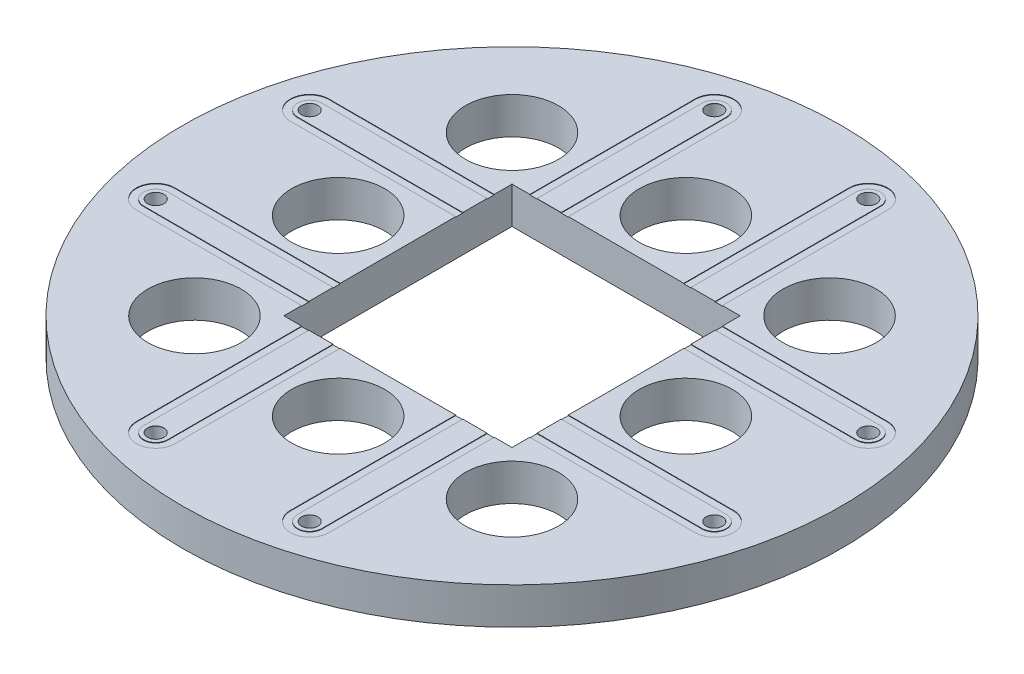
SolidWorks part; units mm, degrees
material "Ceramic Porcelain"
ref_plane "Front Plane" through (0, 0, 0) normal (0, 0, 1) x (1, 0, 0)
ref_plane "Top Plane" through (0, 0, 0) normal (0, 1, 0) x (1, 0, 0)
ref_plane "Right Plane" through (0, 0, 0) normal (1, 0, 0) x (0, 0, -1)
ref_axis "Y Axis" through (0, 0.0762, 0) along (0, -1, 0)
sketch "Boday Sketch" plane through (0, 0, 0) normal (0, 1, 0) x (1, 0, 0)
  circle A0 centre (0, 0) radius 11.557
  dimension "D1" = 23.114
extrude "Body" add sketch "Boday Sketch" against normal blind 1.27
sketch "Copper Sketch" plane through (0, 0, 0) normal (0, 1, 0) x (1, 0, 0)
  circle A0 centre (0, 0) radius 11.557
  dimension "D1" = 23.114
extrude "Copper" add sketch "Copper Sketch" along normal blind 0.0175
sketch "IO Hole Positions" plane through (0, 0, 0) normal (0, 1, 0) x (1, 0, 0)
  line L0 (-11.557, 0) -> (11.557, 0) construction
  circle A1 centre (0, 0) radius 11.557 construction
  point P1 (-2.7, 9.7947)
  point P8 (-2.7, -9.7947)
  dimension "D2" = 2.7
sketch "Gap" plane through (0, 0, 0) normal (0, 1, 0) x (1, 0, 0)
  line L10 (-3.375, 9.7947) -> (-3.375, -9.7947)
  line L11 (-11.557, 0) -> (11.557, 0) construction
  line L12 (-3.375, 0) -> (-2.025, 0) construction
  line L13 (-2.025, -9.7947) -> (-2.025, 9.7947)
  arc A5 (-2.025, 9.7947) -> (-3.375, 9.7947) centre (-2.7, 9.7947) ccw
  arc A6 (-2.025, -9.7947) -> (-3.375, -9.7947) centre (-2.7, -9.7947) cw
  dimension "D1" = 0.675
sketch "Center Sketch" plane through (0, 0, 0) normal (0, 1, 0) x (1, 0, 0)
  line L6 (-3.125, 9.7947) -> (-3.125, -9.7947)
  line L7 (-11.557, 0) -> (11.557, 0) construction
  line L8 (-3.125, 0) -> (-2.275, 0) construction
  line L9 (-2.275, -9.7947) -> (-2.275, 9.7947)
  arc A3 (-2.275, 9.7947) -> (-3.125, 9.7947) centre (-2.7, 9.7947) ccw
  arc A4 (-2.275, -9.7947) -> (-3.125, -9.7947) centre (-2.7, -9.7947) cw
  dimension "D1" = 0.425
extrude "Gap Cut" cut sketch "Gap" along normal through all
extrude "Center" add sketch "Center Sketch" along normal blind 0.0175 separate body
sketch "IO Hole Sketch" plane through (0, 0, 0) normal (0, 1, 0) x (1, 0, 0)
  circle A1 centre (-2.7, 9.7947) radius 0.287
  circle A3 centre (-2.7, -9.7947) radius 0.287
  dimension "D1" = 0.574
  dimension "D2" = 0.574
extrude "IO Hole" cut sketch "IO Hole Sketch" against normal through all and the other way through all
pattern_circular "Gap Cuts" count 4 over 360 about axis through (0, 0.0762, 0) along (0, -1, 0) of "Gap Cut"
pattern_circular "Centers" count 4 over 360 about axis through (0, 0.0762, 0) along (0, -1, 0) of "Center"
pattern_circular "IO Holes" count 4 over 360 about axis through (0, 0.0762, 0) along (0, -1, 0) of "IO Hole"
sketch "Pocket Sketch" plane through (0, 0, 0) normal (0, 1, 0) x (1, 0, 0)
  line L1 (-4, -4) -> (4, -4)
  line L2 (-4, -4) -> (-4, 4)
  line L3 (-4, 4) -> (4, 4)
  line L4 (4, -4) -> (4, 4)
  line L5 (-4, -4) -> (4, 4) construction
  line L6 (-4, 4) -> (4, -4) construction
  point P0 (0, 0)
  dimension "D1" = 8
  dimension "D2" = 8
extrude "Pocket" cut sketch "Pocket Sketch" against normal through all and the other way through all
sketch "Posts" plane through (0, 0, 0) normal (0, 1, 0) x (1, 0, 0)
  circle A0 centre (0, 6.096) radius 1.632
  circle A8 centre (-5.5678, 5.5678) radius 1.6319
  point P0 (0, 6.096)
  point P4 (-5.5678, 5.5678)
  dimension "D2" = 3.2639
  dimension "D4" = 3.2639
  dimension "D1" = 6.096
  dimension "D3" = 7.874
  dimension "D5" = 6.096
extrude "Post Cut" cut sketch "Posts" against normal through all and the other way through all
pattern_circular "Post Cuts" count 4 over 360 about axis through (0, 0.0762, 0) along (0, -1, 0) of "Post Cut"
equation "\"mount_d\"= 0.91in"
equation "\"dieletric_h\"= 0.05in"
equation "\"D1@Boday Sketch\" = \"mount_d\""
equation "\"D1@Body\" = \"dieletric_h\""
equation "\"screw_inner_r\"= 0.415in"
equation "\"io_r\"= 0.4in"
equation "\"io_hole_d\"= 0.574mm"
equation "\"W\"= 0.85mm"
equation "\"G\"= 0.25mm"
equation "\"copper_t\"= 17.5um"
equation "\"silicon_size\"= 8mm"
equation "\"D1@Center\" = \"copper_t\""
equation "\"D1@Copper\"=\"copper_t\""
equation "\"D1@Pocket Sketch\" = \"silicon_size\""
equation "\"D2@Pocket Sketch\" = \"silicon_size\""
equation "\"post_r1\" = 0.24in"
equation "\"post_r2\" = 0.31in"
equation "\"D1@Posts\"=\"post_r1\""
equation "\"post_hole_size\" = 0.1285in"
equation "\"D2@Posts\"=\"post_hole_size\""
equation "\"D3@Posts\"=\"post_r2\""
equation "\"D4@Posts\"=\"post_hole_size\""
equation "\"io_x\" = 2.7mm"
equation "\"D1@IO Hole Positions\"=\"io_r\""
equation "\"D2@IO Hole Positions\"=\"io_x\""
equation "\"D1@IO Hole Sketch\"=\"io_hole_d\""
equation "\"D2@IO Hole Sketch\"=\"io_hole_d\""
equation "\"D1@Gap\"= \"W\" / 2 + \"G\""
equation "\"D1@Center Sketch\"=\"W\" / 2"
equation "\"D5@Posts\"=\"post_r1\""
